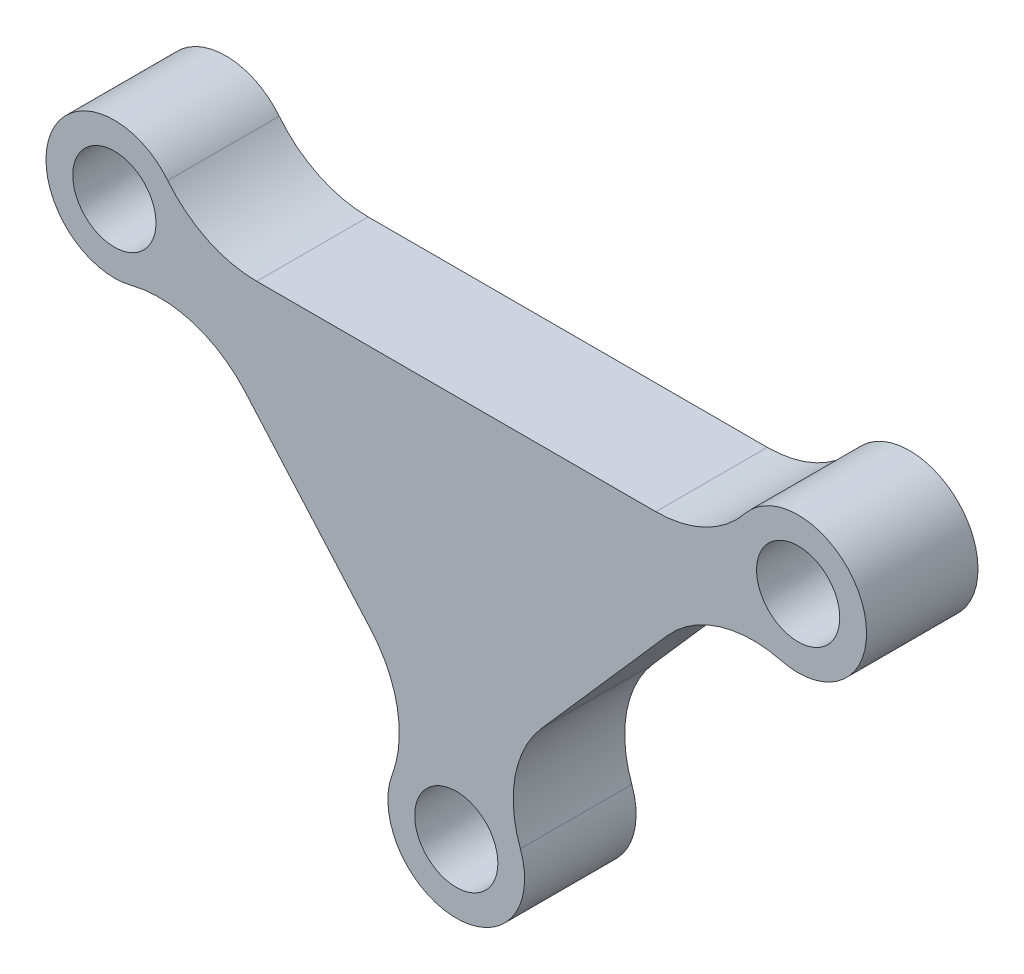
SolidWorks part; units mm, degrees
ref_plane "Plan de face" through (0, 0, 0) normal (0, 0, 1) x (1, 0, 0)
ref_plane "Plan de dessus" through (0, 0, 0) normal (0, 1, 0) x (1, 0, 0)
ref_plane "Plan de droite" through (0, 0, 0) normal (1, 0, 0) x (0, 0, -1)
sketch "Esquisse2" plane through (0, 0, 0) normal (0, 0, 1) x (1, 0, 0)
  line L0 (-13.175, 10) -> (13.175, 10)
  line L1 (13.175, 10) -> (0, -5)
  line L2 (0, -5) -> (-13.175, 10)
  line L3 (0, 0) -> (-13.175, 10) construction
  line L4 (0, 0) -> (13.175, 10) construction
  circle A0 centre (-15, 10) radius 3
  circle A1 centre (-15, 10) radius 1.825
  circle A2 centre (15, 10) radius 3
  circle A3 centre (15, 10) radius 1.825
  circle A4 centre (0, -6.825) radius 3
  circle A5 centre (0, -6.825) radius 1.825
  dimension "D2" = 3.65
  dimension "D3" = 6
  dimension "D1" = 5
  dimension "D4" = 10
  dimension "D5" = 15
extrude "Boss.-Extru.1" add sketch "Esquisse2" along normal blind 4.89 contours A4 L1 A2 L0 A0 L2 | L1 A5 L2 A4 | L1 A4 L2 | A3 | A1 | L0 L1 L2 | A2 | A0 | A4 | A5 region at (-15, 10, 0) region at (0, 5.0202, 0) region at (15, 10, 0) region at (0, -4.2487, 0) region at (-0.5172, -4.5383, 0)
fillet "Congé1" radius 5 6 edges at (-12, 10, 2.445) (-12.2089, 8.9001, 2.445) (-0.9084, -3.9658, 2.445) (12.2089, 8.9001, 2.445) (12, 10, 2.445) (0.9084, -3.9658, 2.445)
